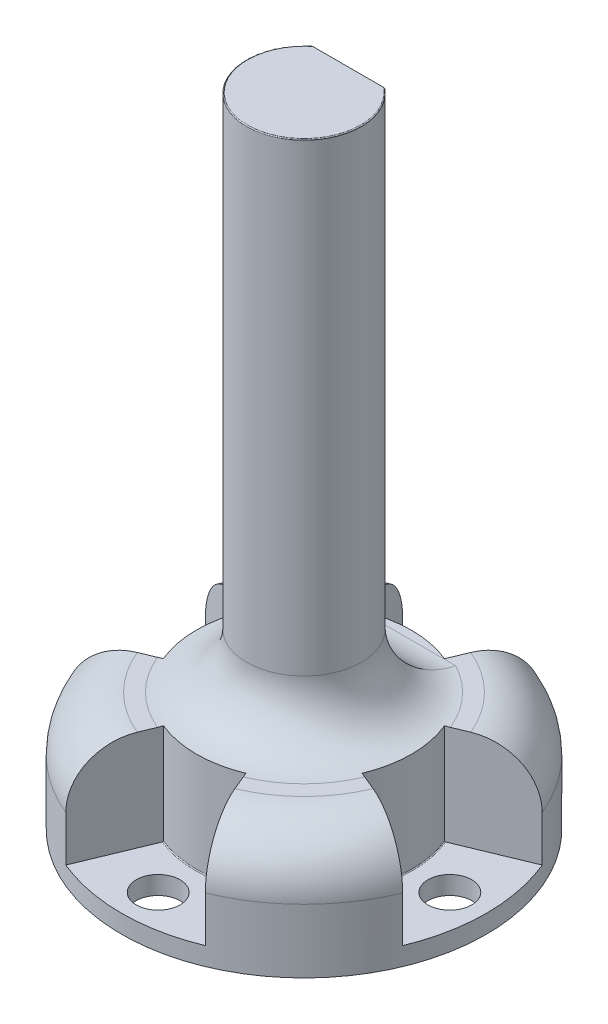
SolidWorks part; units mm, degrees
material "ABS"
ref_plane "Plan de face" through (0, 0, 0) normal (0, 0, 1) x (1, 0, 0)
ref_plane "Plan de dessus" through (0, 0, 0) normal (0, 1, 0) x (1, 0, 0)
ref_plane "Plan de droite" through (0, 0, 0) normal (1, 0, 0) x (0, 0, -1)
sketch "Esquisse2" plane through (0, 0, 0) normal (0, 0, 1) x (1, 0, 0)
  line L0 (0, 35) -> (3.15, 35)
  line L3 (5.9, 3) -> (5.9, 1)
  line L4 (5.9, 1) -> (10, 1)
  line L5 (10, 1) -> (10, 0)
  line L6 (10, 0) -> (4.5, 0)
  line L7 (4.5, 0) -> (4.5, 3)
  line L8 (4.5, 3) -> (0, 3)
  line L9 (0, 3) -> (0, 35)
  line L11 (3.15, 35) -> (3.15, 6.5)
  line L12 (3.15, 6.5) -> (5.9, 6.5)
  line L13 (5.9, 3) -> (5.9, 6.5)
  point P2 (1.575, 35)
  dimension "D1" = 10
  dimension "D2" = 35
  dimension "D3" = 0
  dimension "D4" = 1
  dimension "D5" = 4.5
  dimension "D6" = 2
  dimension "D7" = 6.5
  dimension "D8" = 3
  dimension "D9" = 3.15
  dimension "D10" = 0
  dimension "D12" = 1.4
revolve "Révolution2" add sketch "Esquisse2" angle 360 about L9
sketch "Esquisse3" plane through (0, 35, 0) normal (0, 1, 0) x (1, 0, 0)
  line L1 (-3.6413, 2.4219) -> (2.9365, 2.4219)
  line L2 (-3.6413, 2.4219) -> (-3.6413, 3.808)
  line L3 (-3.6413, 3.808) -> (2.9365, 3.808)
  line L4 (2.9365, 2.4219) -> (2.9365, 3.808)
  dimension "D1" = 6.5779
extrude "Enlèv. mat.-Extru.1" cut sketch "Esquisse3" against normal up to surface (28.5 mm away) contours L4 L3 L2 L1 up to face at (0, 6.5, -3.15)
hole_wizard "Dégagement M21" positions "Esquisse4" profile "Esquisse5" hole size "M2" standard "Ansi Metric" end condition up to next
sketch "Esquisse4" plane through (0, 1, 0) normal (0, 1, 0) x (1, 0, 0)
  line L0 (0, -11) -> (0, 11) construction
  circle A0 centre (0, 0) radius 8 construction
  point P0 (0, 8)
  point P7 (1.1679, 7.9143)
  dimension "D1" = 16
sketch "Esquisse5" plane through (0, 1, -8) normal (1, 0, 0) x (0, 0, 1)
  line L0 (0, 0) -> (0, 1.001)
  line L1 (0, 1.001) -> (1.2, 1.001)
  line L2 (1.2, 1.001) -> (1.2, 0)
  line L5 (1.2, 0) -> (0, 0)
  line L11 (0, -6.35) -> (0, 107.95) construction
  dimension "Diamètre du perçage jusqu'au prochain" = 2.4
  dimension "Profondeur du perçage jusqu'au prochain" = 1.001
pattern_circular "Répétition circulaire1" count 4 over 360 about axis through (0, 1, 0) along (0, -1, 0) of "Dégagement M21"
sketch "Sketch2" plane through (0, 1, 0) normal (0, 1, 0) x (1, 0, 0)
  line L0 (0, 0) -> (-3.8268, 9.2388) construction
  line L1 (0, 0) -> (-9.2388, 3.8268) construction
  line L2 (-2.2578, 5.4509) -> (-3.8268, 9.2388)
  line L3 (-5.4509, 2.2578) -> (-9.2388, 3.8268)
  line L4 (0, -11) -> (0, 11) construction
  circle A0 centre (0, 0) radius 10 construction
  arc A1 (-3.8268, 9.2388) -> (-9.2388, 3.8268) centre (0, 0) ccw
  circle A2 centre (0, 0) radius 5.9 construction
  arc A3 (-2.2578, 5.4509) -> (-5.4509, 2.2578) centre (0, 0) ccw
  point P0 (-8.6767, 4.9714)
  dimension "D1" = 45
  dimension "D2" = 22.5
extrude "Boss-Extrude1" add sketch "Sketch2" along normal up to surface (5.5 mm away) up to face at (0, 6.5, 0.364)
pattern_circular "CirPattern1" count 4 over 360 about axis through (0, 6.5, 0) along (0, -1, 0) of "Boss-Extrude1"
fillet "Congé1" radius 0.05 5 edges at (0, 35, 3.15) (0, 1, -5.9) (5.9, 1, 0) (0, 1, 5.9) (-5.9, 1, 0)
sketch "Sketch1" plane through (0, 3, 0) normal (0, -1, 0) x (1, 0, 0)
  circle A0 centre (0, 0) radius 2.5
  dimension "D1" = 5
extrude "Cut-Extrude1" cut sketch "Sketch1" against normal blind 2
fillet "Fillet1" radius 3 4 edges at (7.0711, 6.5, 7.0711) (7.0711, 6.5, -7.0711) (-7.0711, 6.5, 7.0711) (-7.0711, 6.5, -7.0711)
fillet "Fillet3" radius 3 2 edges at (0, 6.5, 3.15) (0, 6.5, -2.4219)
